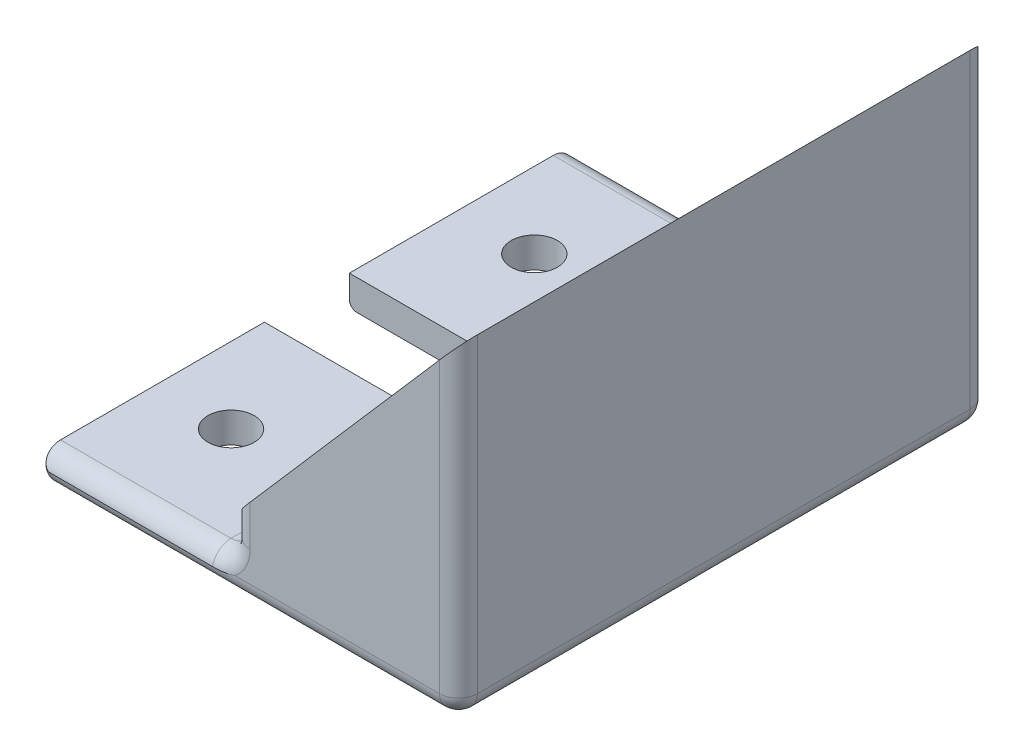
SolidWorks part; units mm, degrees
ref_plane "Front Plane" through (0, 0, 0) normal (0, 0, 1) x (1, 0, 0)
ref_plane "Top Plane" through (0, 0, 0) normal (0, 1, 0) x (1, 0, 0)
ref_plane "Right Plane" through (0, 0, 0) normal (1, 0, 0) x (0, 0, -1)
sketch "Sketch2" plane through (0, 0, 0) normal (0, 0, 1) x (1, 0, 0)
  line L0 (0, 0) -> (30, 34.5111)
  line L1 (30, -9) -> (-25, -9)
  line L2 (-25, -9) -> (-25, -5)
  line L4 (30, 34.5111) -> (30, -9)
  line L5 (-25, -5) -> (0, -5)
  line L6 (0, 0) -> (0, -5)
  dimension "D1" = 4
  dimension "D2" = 25
  dimension "D3" = 5
  dimension "D4" = 30
  dimension "D5" = 25
  dimension "D6" = 131
extrude "Boss-Extrude1" add sketch "Sketch2" along normal mid plane 70 contours L0 L4 L1 L2 L5 L6
sketch "Sketch3" plane through (0, 0, 0) normal (1, 0, 0) x (0, 0, -1)
  line L0 (-35, -9) -> (35, -9) construction
  line L1 (-5.6, -9) -> (5.6, -9)
  line L2 (-5.6, -9) -> (-5.6, -3)
  line L3 (-5.6, -3) -> (5.6, -3)
  line L4 (5.6, -9) -> (5.6, -3)
  line L5 (0, 0) -> (0, -14.0757) construction
  dimension "D1" = 11.2
  dimension "D2" = 6
extrude "Cut-Extrude1" cut sketch "Sketch3" against normal through all
sketch "Sketch4" plane through (0, -5, 0) normal (0, 1, 0) x (1, 0, 0)
  line L0 (0, 0) -> (-40.497, 0) construction
  line L1 (0, -35) -> (0, 35) construction
  line L2 (-25, -35) -> (0, -35) construction
  line L3 (0, -35) -> (0, -5.6) construction
  circle A0 centre (-15, -20) radius 3.05
  circle A1 centre (-15, 20) radius 3.05
  dimension "D3" = 6.1
  dimension "D1" = 15
  dimension "D2" = 15
extrude "Cut-Extrude2" cut sketch "Sketch4" against normal through all
fillet "Fillet1" radius 2.5 11 edges at (0, -2.5, 35) (0, -2.5, -35) (30, -9, 0) (30, 12.7555, -35) (30, 12.7555, 35) (2.5, -9, 35) (-12.5, -5, 35) (2.5, -9, -35) (-12.5, -5, -35) (0, -5, -20.3) (0, -5, 20.3)
fillet "Fillet4" radius 1 4 edges at (-25, -8.4365, -34.0811) (-25, -8.4365, 34.0811) (-25, -9, -19.05) (-25, -9, 19.05)
